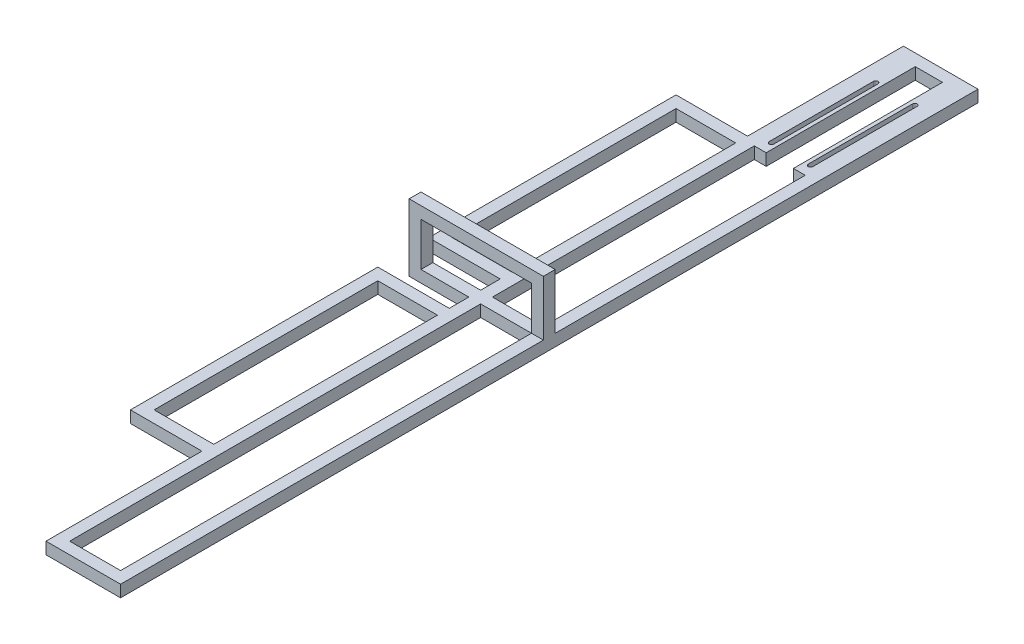
SolidWorks part; units mm, degrees
ref_plane "Front Plane" through (0, 0, 0) normal (0, 0, 1) x (1, 0, 0)
ref_plane "Top Plane" through (0, 0, 0) normal (0, 1, 0) x (1, 0, 0)
ref_plane "Right Plane" through (0, 0, 0) normal (1, 0, 0) x (0, 0, -1)
sketch "Sketch1" plane through (0, 0, 0) normal (0, 1, 0) x (1, 0, 0)
  line L1 (-50, 575) -> (50, 575)
  line L2 (-50, 575) -> (-50, -575)
  line L3 (-50, -575) -> (50, -575)
  line L4 (50, 575) -> (50, -575)
  line L8 (-34.125, 559.125) -> (34.125, 559.125)
  line L9 (34.125, 559.125) -> (34.125, -559.125)
  line L10 (-34.125, -559.125) -> (34.125, -559.125)
  line L11 (-34.125, 559.125) -> (-34.125, -559.125)
  point P4 (0, 575)
  point P6 (50, 0)
  dimension "D1" = 100
  dimension "D2" = 1150
  dimension "D3" = 15.875
extrude "Boss-Extrude1" add sketch "Sketch1" along normal blind 15.875
sketch "Sketch3" plane through (0, 15.875, 0) normal (0, 1, 0) x (1, 0, 0)
  line L0 (-50, 575) -> (-50, -575) construction
  line L1 (-50, 50) -> (-130, 50)
  line L2 (-50, 50) -> (-50, 350)
  line L3 (-50, 350) -> (-130, 350)
  line L4 (-130, 50) -> (-130, 350)
  line L5 (-130, 575) -> (-130, -575) construction
  line L6 (-34.125, 365.875) -> (-145.875, 365.875)
  line L7 (-145.875, 34.125) -> (-145.875, 365.875)
  line L8 (-34.125, 34.125) -> (-145.875, 34.125)
  line L9 (-34.125, 34.125) -> (-34.125, 365.875)
  line L10 (-8.7312, 0) -> (8.7312, 0) construction
  line L11 (-34.125, -34.125) -> (-34.125, -365.875)
  line L12 (-34.125, -34.125) -> (-145.875, -34.125)
  line L13 (-145.875, -34.125) -> (-145.875, -365.875)
  line L14 (-34.125, -365.875) -> (-145.875, -365.875)
  line L15 (-130, -50) -> (-130, -350)
  line L16 (-50, -50) -> (-50, -350)
  line L17 (-50, -50) -> (-130, -50)
  line L18 (-50, -350) -> (-130, -350)
  dimension "D1" = 350
  dimension "D2" = 50
  dimension "D3" = 15.875
extrude "Boss-Extrude2" add sketch "Sketch3" against normal blind 15.875
sketch "Sketch5" plane through (0, 0, 0) normal (0, 0, 1) x (1, 0, 0)
  line L0 (-130, 959.91) -> (-130, -15.875) construction
  line L1 (50, 0) -> (-130, 0)
  line L2 (50, 0) -> (50, 90)
  line L3 (50, 90) -> (-130, 90)
  line L4 (-130, 0) -> (-130, 90)
  line L5 (34.125, 74.125) -> (-114.125, 74.125)
  line L6 (-114.125, 15.875) -> (-114.125, 74.125)
  line L7 (34.125, 15.875) -> (-114.125, 15.875)
  line L8 (34.125, 15.875) -> (34.125, 74.125)
  dimension "D1" = 90
  dimension "D2" = 15.875
extrude "Boss-Extrude3" add sketch "Sketch5" along normal mid plane 15.875
sketch "Sketch6" plane through (0, 0, 0) normal (0, -1, 0) x (1, 0, 0)
  line L6 (-34.125, -559.125) -> (-18.25, -559.125)
  line L7 (-34.125, -559.125) -> (-34.125, -359.125)
  line L8 (-34.125, -359.125) -> (-18.25, -359.125)
  line L9 (-18.25, -559.125) -> (-18.25, -359.125)
  line L10 (34.125, -559.125) -> (18.25, -559.125)
  line L11 (34.125, -559.125) -> (34.125, -359.125)
  line L12 (34.125, -359.125) -> (18.25, -359.125)
  line L13 (18.25, -559.125) -> (18.25, -359.125)
  line L14 (34.125, -559.125) -> (-34.125, -559.125) construction
  dimension "D1" = 15.875
  dimension "D2" = 15.875
  dimension "D4" = 200
extrude "Boss-Extrude4" add sketch "Sketch6" against normal blind 15.875
sketch "Sketch7" plane through (0, 0, 0) normal (0, -1, 0) x (1, 0, 0)
  line L0 (-26.1875, -374.125) -> (-26.1875, -514.125) construction
  line L1 (-23.1875, -374.125) -> (-23.1875, -514.125)
  line L2 (-29.1875, -374.125) -> (-29.1875, -514.125)
  line L3 (26.1875, -374.125) -> (26.1875, -514.125) construction
  line L4 (29.1875, -374.125) -> (29.1875, -514.125)
  line L5 (23.1875, -374.125) -> (23.1875, -514.125)
  line L6 (-18.25, -359.125) -> (-34.125, -359.125) construction
  line L7 (34.125, -359.125) -> (18.25, -359.125) construction
  arc A0 (-23.1875, -374.125) -> (-29.1875, -374.125) centre (-26.1875, -374.125) ccw
  arc A1 (-29.1875, -514.125) -> (-23.1875, -514.125) centre (-26.1875, -514.125) ccw
  arc A2 (29.1875, -374.125) -> (23.1875, -374.125) centre (26.1875, -374.125) ccw
  arc A3 (23.1875, -514.125) -> (29.1875, -514.125) centre (26.1875, -514.125) ccw
  point P2 (-26.1875, -444.125)
  point P7 (26.1875, -444.125)
  point P16 (0, 0)
  point P17 (-26.1875, -359.125)
  point P20 (26.1875, -359.125)
  dimension "D1" = 3
  dimension "D2" = 140
  dimension "D3" = 15
extrude "Cut-Extrude1" cut sketch "Sketch7" against normal blind 15.875
